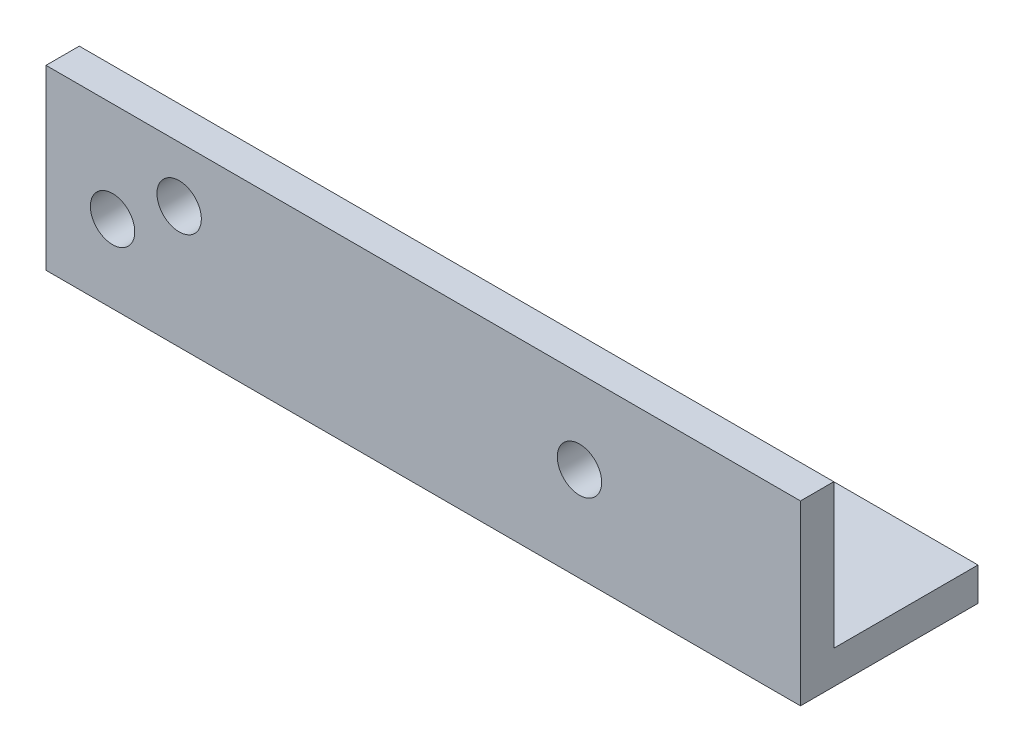
SolidWorks part; units mm, degrees
material "6061 Alloy"
ref_plane "Front Plane" through (0, 0, 0) normal (0, 0, 1) x (1, 0, 0)
ref_plane "Top Plane" through (0, 0, 0) normal (0, 1, 0) x (1, 0, 0)
ref_plane "Right Plane" through (0, 0, 0) normal (1, 0, 0) x (0, 0, -1)
sketch "Sketch1" plane through (0, 0, 0) normal (1, 0, 0) x (0, 0, -1)
  line L0 (0, 0) -> (0, -25.4)
  line L1 (0, -25.4) -> (25.4, -25.4)
  line L2 (25.4, -25.4) -> (25.4, -20.6375)
  line L3 (25.4, -20.6375) -> (4.7625, -20.6375)
  line L4 (4.7625, -20.6375) -> (4.7625, 0)
  line L5 (4.7625, 0) -> (0, 0)
  dimension "D1" = 4.7625
  dimension "D2" = 4.7625
  dimension "D3" = 25.4
  dimension "D4" = 25.4
extrude "Boss-Extrude1" add sketch "Sketch1" along normal blind 107.95
sketch "Sketch3" plane through (0, 0, -4.7625) normal (0, 0, -1) x (-1, 0, 0)
  line L0 (0, -20.6375) -> (0, 0) construction
  line L1 (-107.95, -25.4) -> (0, -25.4) construction
  circle A0 centre (-9.525, -14.2875) radius 3.175
  circle A1 centre (-19.05, -7.9375) radius 3.175
  dimension "D1" = 6.35
  dimension "D2" = 6.35
  dimension "D3" = 9.525
  dimension "D4" = 19.05
  dimension "D5" = 11.1125
  dimension "D6" = 17.4625
extrude "Cut-Extrude1" cut sketch "Sketch3" against normal up to next
sketch "Sketch4" plane through (0, 0, 0) normal (0, 0, 1) x (1, 0, 0)
  circle A0 centre (76.3322, -11.9296) radius 3.175 construction
  circle A1 centre (76.3322, -11.9296) radius 3.175
extrude "Cut-Extrude2" cut sketch "Sketch4" against normal up to next
